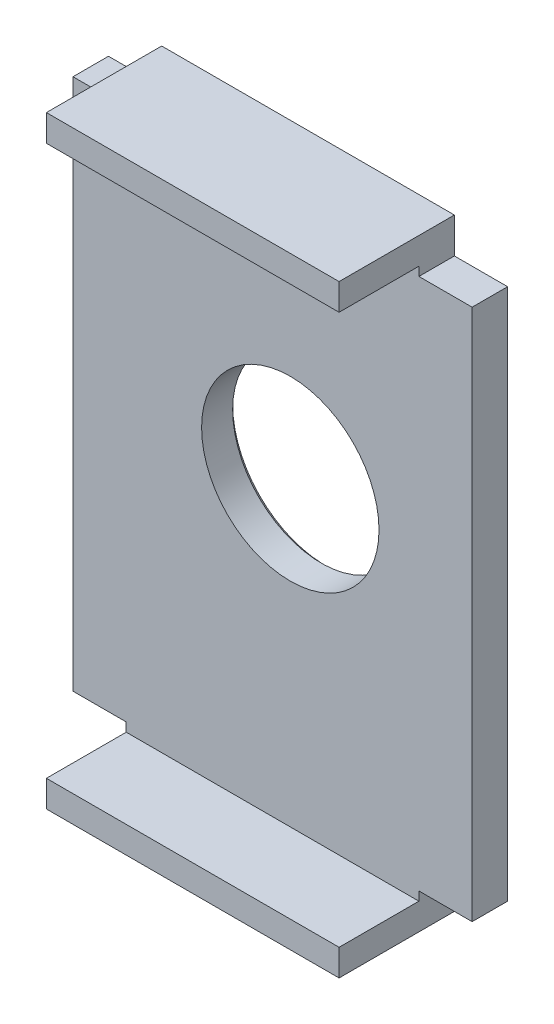
SolidWorks part; units mm, degrees
ref_plane "Front Plane" through (0, 0, 0) normal (0, 0, 1) x (1, 0, 0)
ref_plane "Top Plane" through (0, 0, 0) normal (0, 1, 0) x (1, 0, 0)
ref_plane "Right Plane" through (0, 0, 0) normal (1, 0, 0) x (0, 0, -1)
sketch "Sketch1" plane through (0, 0, 0) normal (0, 0, 1) x (1, 0, 0)
  line L5 (-22.5, -30) -> (22.5, -30)
  line L6 (-22.5, -30) -> (-22.5, 30)
  line L7 (-22.5, 30) -> (22.5, 30)
  line L8 (22.5, -30) -> (22.5, 30)
  line L9 (-22.5, -30) -> (22.5, 30) construction
  line L10 (-22.5, 30) -> (22.5, -30) construction
  circle A2 centre (2, 3) radius 10
  point P0 (0, 0)
  point P5 (2, 9.2858)
  dimension "D3" = 20
  dimension "D4" = 20.5
  dimension "D1" = 60
  dimension "D2" = 45
  dimension "D5" = 3
extrude "Boss-Extrude1" add sketch "Sketch1" along normal mid plane 4
sketch "Sketch3" plane through (0, 0, -2) normal (0, 0, -1) x (-1, 0, 0)
  line L0 (-22.5, 30) -> (22.5, 30) construction
  line L1 (-16.5, 30) -> (16.5, 30)
  line L2 (-16.5, 30) -> (-16.5, 34)
  line L3 (-16.5, 34) -> (16.5, 34)
  line L4 (16.5, 30) -> (16.5, 34)
  line L5 (-22.5, -30) -> (-22.5, 30) construction
  line L6 (22.5, 30) -> (22.5, -30) construction
  line L7 (22.5, -30) -> (-22.5, -30) construction
  line L8 (-16.5, -30) -> (16.5, -30)
  line L9 (-16.5, -30) -> (-16.5, -34)
  line L10 (-16.5, -34) -> (16.5, -34)
  line L11 (16.5, -30) -> (16.5, -34)
  dimension "D1" = 6
  dimension "D2" = 6
  dimension "D3" = 4
extrude "Boss-Extrude3" add sketch "Sketch3" against normal blind 13
chamfer "Chamfer1" distance 0.5 angle 45 1 edges at (12, 3, -2)
sketch "Sketch4" plane through (0, 0, 11) normal (0, 0, 1) x (1, 0, 0)
  line L0 (16.5, 34) -> (16.5, 30) construction
  line L1 (-16.5, 30) -> (16.5, 30)
  line L2 (-16.5, 30) -> (-16.5, 31)
  line L3 (-16.5, 31) -> (16.5, 31)
  line L4 (16.5, 30) -> (16.5, 31)
  line L5 (-16.5, -34) -> (-16.5, -30) construction
  line L6 (16.5, -30) -> (-16.5, -30)
  line L7 (16.5, -30) -> (16.5, -31)
  line L8 (16.5, -31) -> (-16.5, -31)
  line L9 (-16.5, -30) -> (-16.5, -31)
  dimension "D1" = 1
extrude "Cut-Extrude1" cut sketch "Sketch4" against normal up to vertex (9 mm away) up to point (16.5, -30, 2)
equation "\"padding\"=6"
equation "\"wall_thick_ness\"=4"
equation "\"D1@Sketch3\"=\"padding\""
equation "\"D2@Sketch3\"=\"padding\""
equation "\"D3@Sketch3\"=\"wall_thick_ness\""
equation "\"D1@Boss-Extrude1\"=\"wall_thick_ness\""
